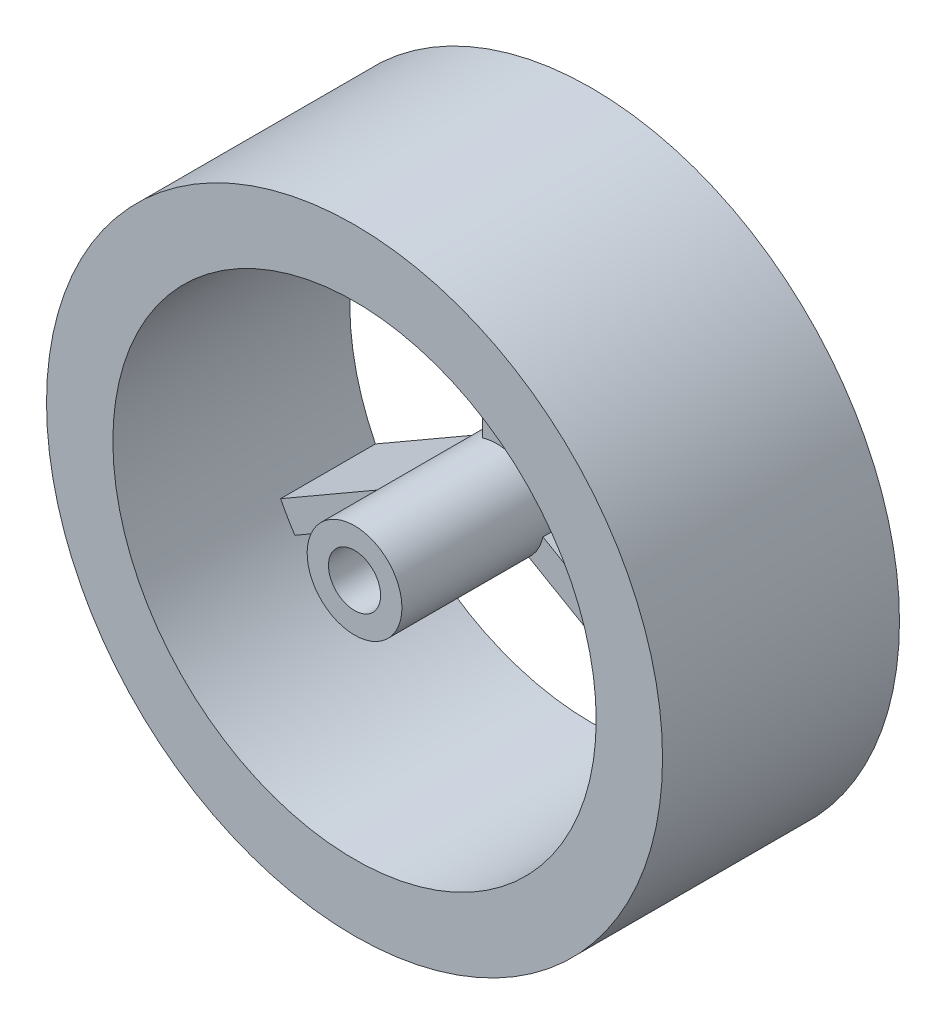
SolidWorks part; units mm, degrees
ref_plane "前视基准面" through (0, 0, 0) normal (0, 0, 1) x (1, 0, 0)
ref_plane "上视基准面" through (0, 0, 0) normal (0, 1, 0) x (1, 0, 0)
ref_plane "右视基准面" through (0, 0, 0) normal (1, 0, 0) x (0, 0, -1)
other "Configuration Table"
sketch "草图1" plane through (0, 0, 0) normal (0, 0, 1) x (1, 0, 0)
  circle A0 centre (0, 0) radius 25.5
  circle A1 centre (0, 0) radius 32.5
  dimension "D1" = 51
  dimension "D2" = 65
extrude "凸台-拉伸1" add sketch "草图1" along normal blind 25
sketch "草图2" plane through (0, 0, 0) normal (0, 0, 1) x (1, 0, 0)
  line L0 (-1.5, 4.7697) -> (-1.5, 25.4558)
  line L1 (1.5, 4.7697) -> (1.5, 25.4558)
  line L2 (0, 0) -> (0, 25.5) construction
  line L3 (4.8807, -1.0858) -> (22.7954, -11.4289)
  line L4 (3.3807, -3.6839) -> (21.2954, -14.027)
  line L5 (-3.3807, -3.6839) -> (-21.2954, -14.027)
  line L6 (-4.8807, -1.0858) -> (-22.7954, -11.4289)
  circle A0 centre (0, 0) radius 2.75
  circle A1 centre (0, 0) radius 5
  circle A2 centre (0, 0) radius 25.5
  circle A3 centre (0, 0) radius 25.5 construction
  point P22 (0, 0)
  dimension "D1" = 5.5
  dimension "D2" = 10
  dimension "D3" = 3
  dimension "D4" = 3
extrude "凸台-拉伸2" add sketch "草图2" along normal blind 10 contours A1 L2 A2 L0 | L2 A1 L1 A2 | L6 A2 L5 A1 | L4 A2 L3 A1 region at (-0.7511, 15.2045, 0) region at (-13.1675, -7.6023, 0) region at (0.7511, 15.2045, 0) region at (13.1675, -7.6023, 0)
extrude "凸台-拉伸3" add sketch "草图2<3>" along normal blind 25 contours A0 A1 region at (0, 4.8586, 0)
sketch "草图2<3>" plane through (0, 0, 0) normal (0, 0, 1) x (1, 0, 0) same geometry as "草图2"
